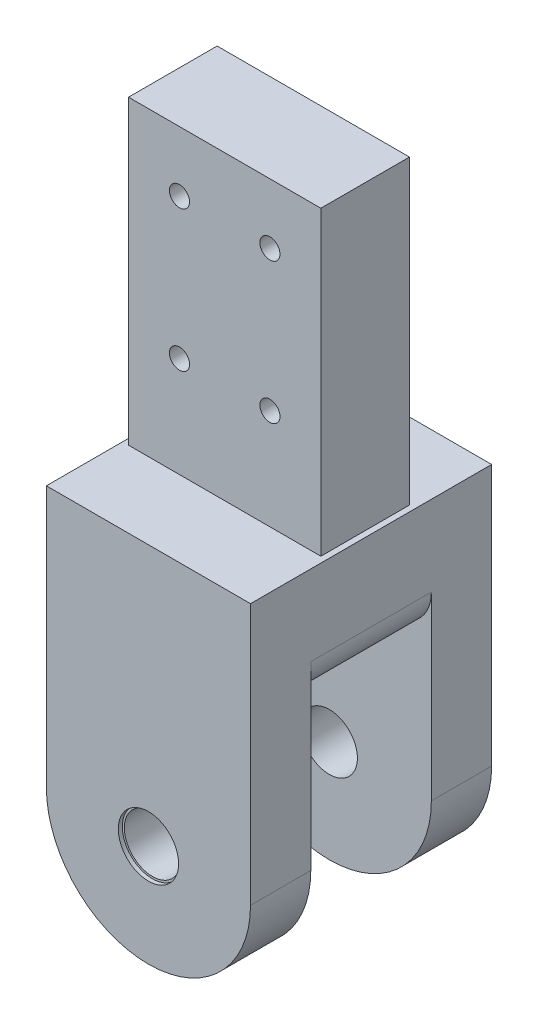
SolidWorks part; units mm, degrees
ref_plane "Front Plane" through (0, 0, 0) normal (0, 0, 1) x (1, 0, 0)
ref_plane "Top Plane" through (0, 0, 0) normal (0, 1, 0) x (1, 0, 0)
ref_plane "Right Plane" through (0, 0, 0) normal (1, 0, 0) x (0, 0, -1)
sketch "Sketch1" plane through (0, 0, 0) normal (0, 0, 1) x (1, 0, 0)
  line L0 (-25.4, 0) -> (-25.4, 140)
  line L1 (-25.4, 140) -> (25.4, 140)
  line L2 (25.4, 140) -> (25.4, 0)
  line L4 (-11.25, 125) -> (11.25, 125) construction
  line L5 (-11.25, 125) -> (-11.25, 90) construction
  line L6 (-11.25, 90) -> (11.25, 90) construction
  line L7 (11.25, 125) -> (11.25, 90) construction
  circle A0 centre (0, 0) radius 7
  arc A1 (-25.4, 0) -> (25.4, 0) centre (0, 0) ccw
  circle A2 centre (-11.25, 125) radius 2.5
  circle A3 centre (11.25, 125) radius 2.5
  circle A4 centre (11.25, 90) radius 2.5
  circle A5 centre (-11.25, 90) radius 2.5
  point P13 (0, 90)
  dimension "D1" = 14
  dimension "D4" = 5
  dimension "D2" = 50.8
  dimension "D3" = 140
  dimension "D5" = 35
  dimension "D6" = 15
  dimension "D7" = 22.5
extrude "Boss-Extrude1" add sketch "Sketch1" along normal mid plane 60
sketch "Sketch2" plane through (25.4, 0, 0) normal (1, 0, 0) x (0, 0, -1)
  line L0 (-30, -25.4) -> (30, -25.4) construction
  line L1 (-15, 35) -> (15, 35)
  line L2 (-15, 35) -> (-15, -25.4)
  line L3 (-15, -25.4) -> (15, -25.4)
  line L4 (15, 35) -> (15, -25.4)
  line L5 (-30, 0) -> (30, 0) construction
  point P8 (0, 0)
  point P9 (0, 35)
  dimension "D1" = 30
  dimension "D2" = 35
extrude "Cut-Extrude1" cut sketch "Sketch2" against normal through all
sketch "Sketch3" plane through (0, 0, 30) normal (0, 0, 1) x (1, 0, 0)
  circle A0 centre (0, 0) radius 7.5
  dimension "D1" = 15
extrude "Cut-Extrude2" cut sketch "Sketch3" against normal blind 1
sketch "Sketch4" plane through (0, 0, -30) normal (0, 0, -1) x (-1, 0, 0)
  circle A0 centre (0, 0) radius 7.5
  dimension "D1" = 15
extrude "Cut-Extrude3" cut sketch "Sketch4" against normal blind 1
sketch "Sketch6" plane through (25.4, 0, 0) normal (1, 0, 0) x (0, 0, -1)
  line L1 (-30, 140) -> (-12.7, 140)
  line L2 (-30, 140) -> (-30, 65)
  line L3 (-30, 65) -> (-12.7, 65)
  line L4 (-12.7, 140) -> (-12.7, 65)
  line L5 (30, 140) -> (12.7, 140)
  line L6 (30, 140) -> (30, 65)
  line L7 (30, 65) -> (12.7, 65)
  line L8 (12.7, 140) -> (12.7, 65)
  dimension "D1" = 25.4
  dimension "D2" = 75
extrude "Cut-Extrude4" cut sketch "Sketch6" against normal through all
sketch "Sketch7" plane through (0, 65, 0) normal (0, 1, 0) x (1, 0, 0)
  line L0 (-25.4, 12.7) -> (-25.4, 30) construction
  line L1 (-23.93, -11.025) -> (23.93, -11.025)
  line L2 (-23.93, -11.025) -> (-23.93, 11.025)
  line L3 (-23.93, 11.025) -> (23.93, 11.025)
  line L4 (23.93, -11.025) -> (23.93, 11.025)
  line L5 (-23.93, -11.025) -> (23.93, 11.025) construction
  line L6 (-23.93, 11.025) -> (23.93, -11.025) construction
  line L7 (25.4, -12.7) -> (-25.4, -12.7)
  line L8 (25.4, -12.7) -> (25.4, 12.7)
  line L9 (25.4, 12.7) -> (-25.4, 12.7)
  line L10 (-25.4, -12.7) -> (-25.4, 12.7)
  line L11 (25.4, -12.7) -> (-25.4, 12.7) construction
  line L12 (25.4, 12.7) -> (-25.4, -12.7) construction
  line L13 (-25.4, 12.7) -> (25.4, 12.7) construction
  point P0 (0, 0)
  point P6 (0, 0)
  dimension "D1" = 47.86
  dimension "D2" = 22.05
extrude "Cut-Extrude5" cut sketch "Sketch7" along normal through all
fillet "Fillet1" radius 10 2 edges at (25.4, 35, 0) (-25.4, 35, 0)
